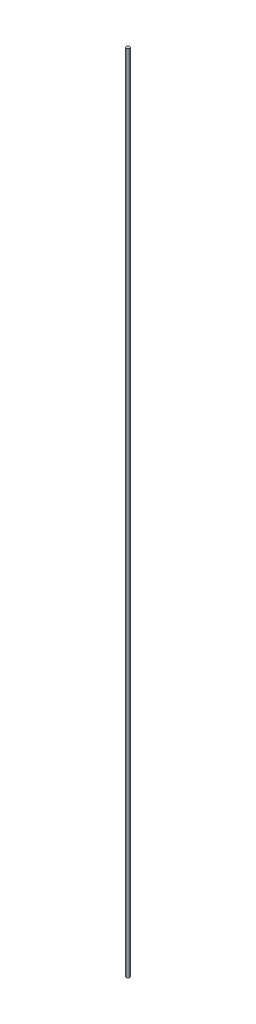
SolidWorks part; units mm, degrees
ref_plane "Front Plane" through (0, 0, 0) normal (0, 0, 1) x (1, 0, 0)
ref_plane "Top Plane" through (0, 0, 0) normal (0, 1, 0) x (1, 0, 0)
ref_plane "Right Plane" through (0, 0, 0) normal (1, 0, 0) x (0, 0, -1)
sketch "Sketch1" plane through (0, 0, 0) normal (0, 1, 0) x (1, 0, 0)
  circle A0 centre (0, 0) radius 0.635
  dimension "D1" = 1.27
extrude "Boss-Extrude1" add sketch "Sketch1" along normal blind 304.8
